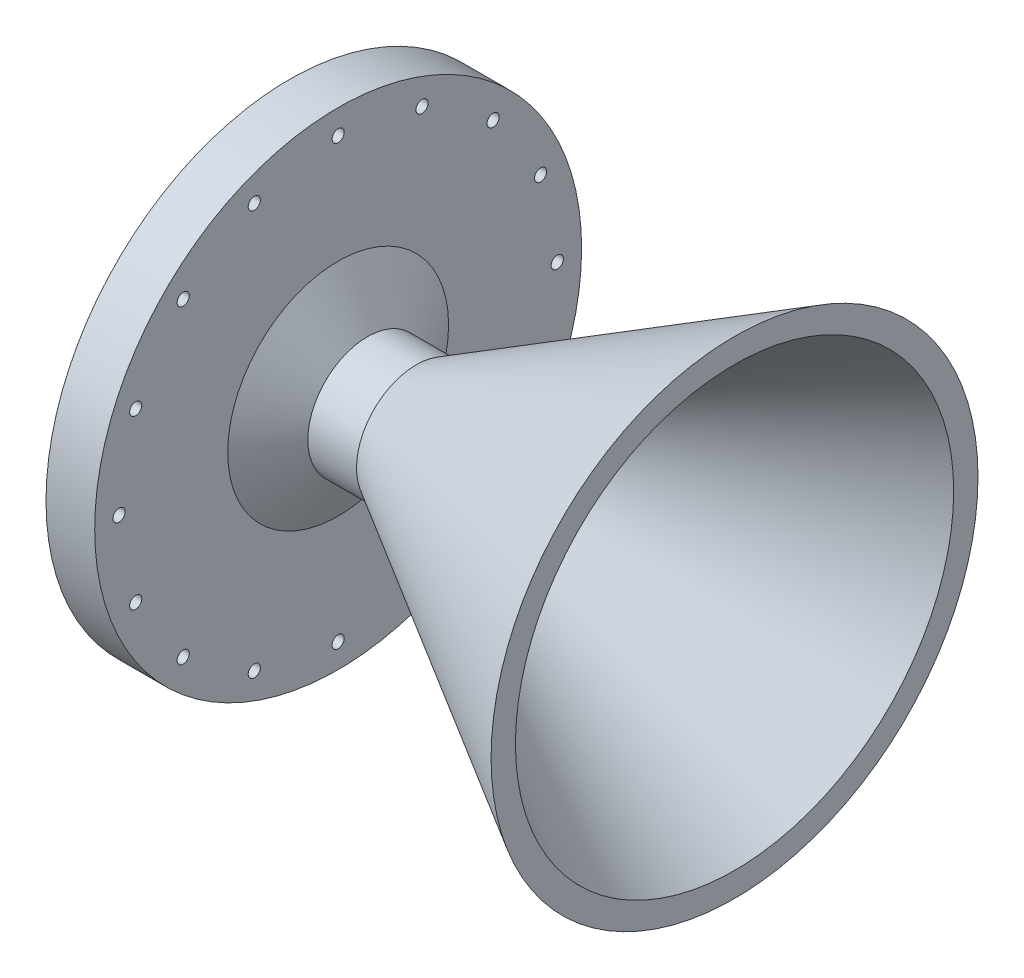
SolidWorks part; units mm, degrees
material "C (Graphite)"
ref_plane "Front Plane" through (0, 0, 0) normal (0, 0, 1) x (1, 0, 0)
ref_plane "Top Plane" through (0, 0, 0) normal (0, 1, 0) x (1, 0, 0)
ref_plane "Right Plane" through (0, 0, 0) normal (1, 0, 0) x (0, 0, -1)
sketch "Sketch1" plane through (0, 0, 0) normal (0, 0, 1) x (1, 0, 0)
  line L0 (0, 0) -> (215.3765, 0) construction
  line L1 (0, 0) -> (0, 93.6004) construction
  line L2 (0, 15.5575) -> (83.0388, 63.5)
  line L3 (0, 7.9375) -> (83.0388, 57.15)
  line L4 (83.0388, 63.5) -> (83.0388, 57.15)
  line L9 (0, 15.5575) -> (-12.7, 15.5575)
  line L10 (0, 7.9375) -> (-12.7, 7.9375)
  line L14 (-12.7, 15.5575) -> (-20.3473, 28.803)
  line L22 (-12.7, 7.9375) -> (-33.0473, 41.275)
  line L23 (-33.0473, 50.8) -> (-33.0473, 41.275)
  line L24 (-33.0473, 50.8) -> (-33.0473, 63.5)
  line L25 (-33.0473, 63.5) -> (-20.3473, 63.5)
  line L26 (-20.3473, 63.5) -> (-20.3473, 28.803)
  dimension "D1" = 6.35
  dimension "D2" = 7.62
  dimension "D3" = 7.9375
  dimension "D4" = 9.525
  dimension "D5" = 12.7
  dimension "D6" = 63.5
  dimension "D7" = 12.7
  dimension "D8" = 30
  dimension "D9" = 60
  dimension "D10" = 50.8
  dimension "D11" = 12.7
  dimension "D12" = 12.7
revolve "Revolve1" add sketch "Sketch1" angle 360 about L0
sketch "Sketch2" plane through (-33.0473, 0, 0) normal (-1, 0, 0) x (0, 0, 1)
  circle A0 centre (0, 0) radius 47.625
  circle A1 centre (0, 0) radius 50.0062
  dimension "D1" = 100.0125
  dimension "D2" = 95.25
extrude "Cut-Extrude1" cut sketch "Sketch2" against normal blind 1.1906
sketch "Sketch3" plane through (-33.0473, 0, 0) normal (-1, 0, 0) x (0, 0, 1)
  circle A0 centre (0, 57.15) radius 1.5875
  circle A1 centre (21.8704, 52.7997) radius 1.5875
  circle A2 centre (40.4112, 40.4112) radius 1.5875
  circle A3 centre (52.7997, 21.8704) radius 1.5875
  circle A4 centre (57.15, 0) radius 1.5875
  circle A5 centre (52.7997, -21.8704) radius 1.5875
  circle A6 centre (40.4112, -40.4112) radius 1.5875
  circle A7 centre (21.8704, -52.7997) radius 1.5875
  circle A8 centre (0, -57.15) radius 1.5875
  circle A9 centre (-21.8704, -52.7997) radius 1.5875
  circle A10 centre (-40.4112, -40.4112) radius 1.5875
  circle A11 centre (-52.7997, -21.8704) radius 1.5875
  circle A12 centre (-57.15, 0) radius 1.5875
  circle A13 centre (-52.7997, 21.8704) radius 1.5875
  circle A14 centre (-40.4112, 40.4112) radius 1.5875
  circle A15 centre (-21.8704, 52.7997) radius 1.5875
  point P36 (0, 0)
  dimension "D1" = 3.175
  dimension "D2" = 57.15
  dimension "D3" = 16
extrude "Cut-Extrude2" cut sketch "Sketch3" against normal up to next
